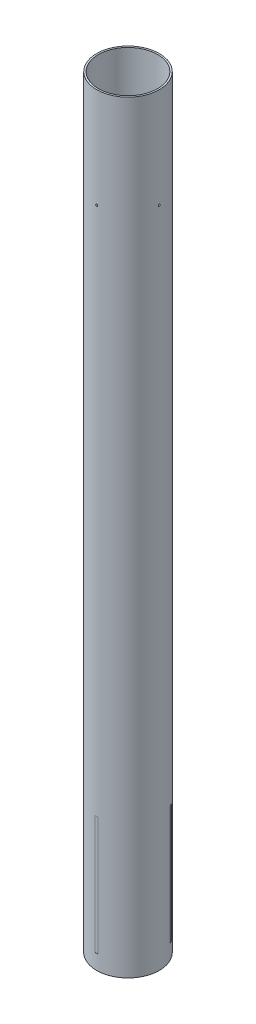
SolidWorks part; units mm, degrees
ref_plane "Front Plane" through (0, 0, 0) normal (0, 0, 1) x (1, 0, 0)
ref_plane "Top Plane" through (0, 0, 0) normal (0, 1, 0) x (1, 0, 0)
ref_plane "Right Plane" through (0, 0, 0) normal (1, 0, 0) x (0, 0, -1)
sketch "Sketch1" plane through (0, 0, 0) normal (0, 1, 0) x (1, 0, 0)
  circle A0 centre (0, 0) radius 53.721
  circle A1 centre (0, 0) radius 50.8
  dimension "D1" = 107.442
  dimension "D2" = 101.6
extrude "Tube Extrusion" add sketch "Sketch1" along normal blind 1308.1
ref_plane "Plane1" through (0, 0, 53.721) normal (0, 0, 1) x (1, 0, 0)
sketch "Sketch2" plane through (0, 0, 53.721) normal (0, 0, 1) x (1, 0, 0)
  line L0 (0, 1308.1) -> (0, 0) construction
  line L3 (53.721, 1308.1) -> (-53.721, 1308.1) construction
  circle A0 centre (0, 1136.65) radius 1.6383
  dimension "D1" = 3.2766
  dimension "D2" = 1136.65
extrude "Engine Block Hole" cut sketch "Sketch2" against normal up to next
pattern_circular "CirPattern1" count 4 over 360 about axis through (0, 1308.1, 0) along (0, -1, 0) of "Engine Block Hole"
sketch "Sketch3" plane through (0, 0, 53.721) normal (0, 0, 1) x (1, 0, 0)
  line L0 (0, 0) -> (0, 25.4) construction
  line L1 (-53.721, 0) -> (53.721, 0) construction
  line L3 (-2.667, 228.6) -> (2.667, 228.6)
  line L4 (-2.667, 228.6) -> (-2.667, 25.4)
  line L5 (-2.667, 25.4) -> (2.667, 25.4)
  line L6 (2.667, 228.6) -> (2.667, 25.4)
  point P8 (0, 25.4)
  dimension "D1" = 25.4
  dimension "D2" = 203.2
  dimension "D3" = 5.334
extrude "Fin Slots" cut sketch "Sketch3" against normal blind 0.254
pattern_circular "CirPattern2" count 3 over 360 about axis through (0, 1308.1, 0) along (0, -1, 0) of "Fin Slots"
